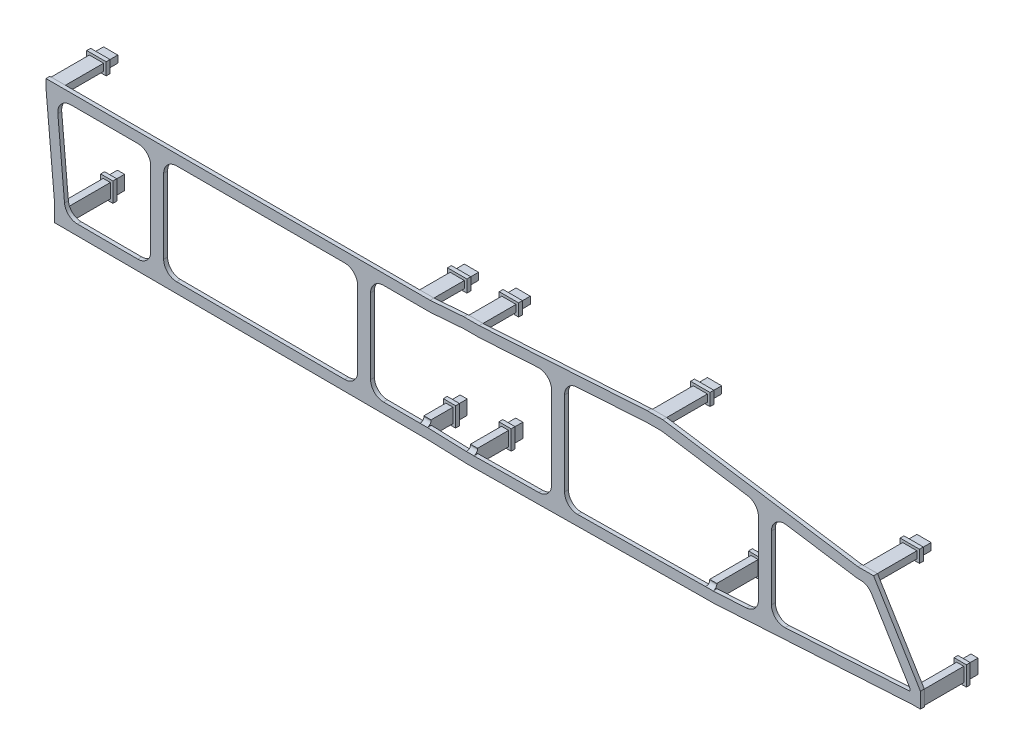
SolidWorks part; units mm, degrees
ref_plane "Front Plane" through (0, 0, 0) normal (0, 0, 1) x (1, 0, 0)
ref_plane "Top Plane" through (0, 0, 0) normal (0, 1, 0) x (1, 0, 0)
ref_plane "Right Plane" through (0, 0, 0) normal (1, 0, 0) x (0, 0, -1)
ref_plane "Plane11" through (0, 0, 7) normal (0, 0, 1) x (1, 0, 0)
ref_plane "Plane12" through (0, 0, 27) normal (0, 0, 1) x (1, 0, 0)
sketch "Sketch13" plane through (0, 0, 27) normal (0, 0, 1) x (1, 0, 0)
  line L0 (-277.75, -90) -> (-284.25, -90)
  line L1 (-284.25, -90) -> (-284.25, -78)
  line L2 (-284.25, -78) -> (-291, -3.25)
  line L3 (-291, -3.25) -> (-291, 3.25)
  line L4 (-291, 3.25) -> (-279, 3.25)
  line L5 (-279, 3.25) -> (-6, 3.25)
  line L6 (-6, 3.25) -> (6, 3.25)
  line L7 (6, 3.25) -> (32, 5.25)
  line L8 (32, 5.25) -> (44, 5.25)
  line L9 (44, 5.25) -> (174, 13.25)
  line L10 (174, 13.25) -> (186, 13.25)
  line L11 (186, 13.25) -> (337, -9.75)
  line L12 (337, -9.75) -> (349, -9.75)
  line L13 (349, -9.75) -> (385.25, -69)
  line L14 (385.25, -69) -> (385.25, -81)
  line L15 (385.25, -81) -> (378.75, -81)
  line L16 (378.75, -81) -> (225.25, -90)
  line L17 (225.25, -90) -> (218.75, -90)
  line L18 (218.75, -90) -> (40.25, -92)
  line L19 (40.25, -92) -> (33.75, -92)
  line L20 (33.75, -92) -> (4.25, -91)
  line L21 (4.25, -91) -> (-2.25, -91)
  line L22 (-2.25, -91) -> (-277.75, -90)
  line L23 (186, 13.25) -> (186, 6.75) construction
extrude "STUD LINK" add sketch "Sketch13" along normal blind 3
ref_plane "Plane1" through (0, 0, 0) normal (0, 0, 1) x (1, 0, 0)
ref_plane "Plane2" through (0, 0, -2) normal (0, 0, 1) x (1, 0, 0)
ref_plane "Plane3" through (0, 0, -8) normal (0, 0, 1) x (1, 0, 0)
ref_plane "Plane4" through (0, 0, 7) normal (0, 0, 1) x (1, 0, 0)
ref_plane "Plane5" through (0, 0, 0) normal (0, 0, 1) x (1, 0, 0)
ref_plane "Plane6" through (0, 0, -8) normal (0, 0, 1) x (1, 0, 0)
ref_plane "Plane7" through (0, 0, -7) normal (0, 0, 1) x (1, 0, 0)
ref_plane "Plane8" through (0, 0, -7) normal (0, 0, 1) x (1, 0, 0)
ref_plane "Plane9" through (0, 0, -6) normal (0, 0, 1) x (1, 0, 0)
ref_plane "Plane10" through (0, 0, -10) normal (0, 0, 1) x (1, 0, 0)
sketch "Sketch1" plane through (0, 0, 0) normal (0, 0, 1) x (1, 0, 0)
  line L8 (-5.5, 2.75) -> (-5.5, -2.75)
  line L9 (-5.5, -2.75) -> (5.5, -2.75)
  line L10 (5.5, -2.75) -> (5.5, 2.75)
  line L11 (5.5, 2.75) -> (-5.5, 2.75)
  line L12 (-5.5, 2.75) -> (-5.5, -2.75)
  line L13 (-5.5, -2.75) -> (5.5, -2.75)
  line L14 (5.5, -2.75) -> (5.5, 2.75)
  line L15 (5.5, 2.75) -> (-5.5, 2.75)
  dimension "D1" = 0.5
extrude "Boss-Extrude1" add sketch "Sketch1" against normal blind 8 and the other way up to next
sketch "Sketch2" plane through (0, 0, -2) normal (0, 0, 1) x (1, 0, 0)
  line L8 (43.5, 4.75) -> (32.5, 4.75)
  line L9 (43.5, -0.75) -> (43.5, 4.75)
  line L10 (32.5, -0.75) -> (43.5, -0.75)
  line L11 (32.5, 4.75) -> (32.5, -0.75)
  line L12 (43.5, 4.75) -> (32.5, 4.75)
  line L13 (43.5, -0.75) -> (43.5, 4.75)
  line L14 (32.5, -0.75) -> (43.5, -0.75)
  line L15 (32.5, 4.75) -> (32.5, -0.75)
  dimension "D1" = 0.5
extrude "Boss-Extrude2" add sketch "Sketch2" against normal blind 8 and the other way up to next separate body
sketch "Sketch3" plane through (0, 0, -8) normal (0, 0, 1) x (1, 0, 0)
  line L16 (185.5, 12.75) -> (174.5, 12.75)
  line L17 (185.5, 7.25) -> (185.5, 12.75)
  line L18 (174.5, 7.25) -> (185.5, 7.25)
  line L19 (174.5, 12.75) -> (174.5, 7.25)
  line L20 (185.5, 12.75) -> (174.5, 12.75)
  line L21 (185.5, 7.25) -> (185.5, 12.75)
  line L22 (174.5, 7.25) -> (185.5, 7.25)
  line L23 (174.5, 12.75) -> (174.5, 7.25)
  dimension "D1" = 0.5
extrude "Boss-Extrude3" add sketch "Sketch3" against normal blind 8 and the other way up to next separate body
sketch "Sketch4" plane through (0, 0, 7) normal (0, 0, 1) x (1, 0, 0)
  line L8 (3.75, -79.5) -> (-1.75, -79.5)
  line L9 (3.75, -90.5) -> (3.75, -79.5)
  line L10 (-1.75, -90.5) -> (3.75, -90.5)
  line L11 (-1.75, -79.5) -> (-1.75, -90.5)
  line L12 (3.75, -79.5) -> (-1.75, -79.5)
  line L13 (3.75, -90.5) -> (3.75, -79.5)
  line L14 (-1.75, -90.5) -> (3.75, -90.5)
  line L15 (-1.75, -79.5) -> (-1.75, -90.5)
  dimension "D1" = 0.5
extrude "Boss-Extrude4" add sketch "Sketch4" against normal blind 8 and the other way up to next separate body
sketch "Sketch5" plane through (0, 0, 0) normal (0, 0, 1) x (1, 0, 0)
  line L16 (34.25, -80.5) -> (34.25, -91.5)
  line L17 (39.75, -80.5) -> (34.25, -80.5)
  line L18 (39.75, -91.5) -> (39.75, -80.5)
  line L19 (34.25, -91.5) -> (39.75, -91.5)
  line L20 (34.25, -80.5) -> (34.25, -91.5)
  line L21 (39.75, -80.5) -> (34.25, -80.5)
  line L22 (39.75, -91.5) -> (39.75, -80.5)
  line L23 (34.25, -91.5) -> (39.75, -91.5)
  dimension "D1" = 0.5
extrude "Boss-Extrude5" add sketch "Sketch5" against normal blind 8 and the other way up to next separate body
sketch "Sketch6" plane through (0, 0, -8) normal (0, 0, 1) x (1, 0, 0)
  line L8 (224.75, -78.5) -> (219.25, -78.5)
  line L9 (219.25, -78.5) -> (219.25, -89.5)
  line L10 (219.25, -89.5) -> (224.75, -89.5)
  line L11 (224.75, -89.5) -> (224.75, -78.5)
  line L12 (224.75, -78.5) -> (219.25, -78.5)
  line L13 (219.25, -78.5) -> (219.25, -89.5)
  line L14 (219.25, -89.5) -> (224.75, -89.5)
  line L15 (224.75, -89.5) -> (224.75, -78.5)
  dimension "D1" = 0.5
extrude "Boss-Extrude6" add sketch "Sketch6" against normal blind 8 and the other way up to next separate body
sketch "Sketch7" plane through (0, 0, -7) normal (0, 0, 1) x (1, 0, 0)
  line L8 (348.5, -10.25) -> (337.5, -10.25)
  line L9 (348.5, -15.75) -> (348.5, -10.25)
  line L10 (337.5, -15.75) -> (348.5, -15.75)
  line L11 (337.5, -10.25) -> (337.5, -15.75)
  line L12 (348.5, -10.25) -> (337.5, -10.25)
  line L13 (348.5, -15.75) -> (348.5, -10.25)
  line L14 (337.5, -15.75) -> (348.5, -15.75)
  line L15 (337.5, -10.25) -> (337.5, -15.75)
  dimension "D1" = 0.5
extrude "Boss-Extrude7" add sketch "Sketch7" against normal blind 8 and the other way up to next separate body
sketch "Sketch8" plane through (0, 0, -7) normal (0, 0, 1) x (1, 0, 0)
  line L8 (384.75, -69.5) -> (379.25, -69.5)
  line L9 (384.75, -80.5) -> (384.75, -69.5)
  line L10 (379.25, -80.5) -> (384.75, -80.5)
  line L11 (379.25, -69.5) -> (379.25, -80.5)
  line L12 (384.75, -69.5) -> (379.25, -69.5)
  line L13 (384.75, -80.5) -> (384.75, -69.5)
  line L14 (379.25, -80.5) -> (384.75, -80.5)
  line L15 (379.25, -69.5) -> (379.25, -80.5)
  dimension "D1" = 0.5
extrude "Boss-Extrude8" add sketch "Sketch8" against normal blind 8 and the other way up to next separate body
sketch "Sketch9" plane through (0, 0, -6) normal (0, 0, 1) x (1, 0, 0)
  line L8 (-279.5, 2.75) -> (-290.5, 2.75)
  line L9 (-279.5, -2.75) -> (-279.5, 2.75)
  line L10 (-290.5, -2.75) -> (-279.5, -2.75)
  line L11 (-290.5, 2.75) -> (-290.5, -2.75)
  line L12 (-279.5, 2.75) -> (-290.5, 2.75)
  line L13 (-279.5, -2.75) -> (-279.5, 2.75)
  line L14 (-290.5, -2.75) -> (-279.5, -2.75)
  line L15 (-290.5, 2.75) -> (-290.5, -2.75)
  dimension "D1" = 0.5
extrude "Boss-Extrude9" add sketch "Sketch9" against normal blind 8 and the other way up to next separate body
sketch "Sketch10" plane through (0, 0, -10) normal (0, 0, 1) x (1, 0, 0)
  line L8 (-278.25, -78.5) -> (-283.75, -78.5)
  line L9 (-278.25, -89.5) -> (-278.25, -78.5)
  line L10 (-283.75, -89.5) -> (-278.25, -89.5)
  line L11 (-283.75, -78.5) -> (-283.75, -89.5)
  line L12 (-278.25, -78.5) -> (-283.75, -78.5)
  line L13 (-278.25, -89.5) -> (-278.25, -78.5)
  line L14 (-283.75, -89.5) -> (-278.25, -89.5)
  line L15 (-283.75, -78.5) -> (-283.75, -89.5)
  dimension "D1" = 0.5
extrude "Boss-Extrude10" add sketch "Sketch10" against normal blind 8 and the other way up to next (37 mm away) separate body
sketch "Sketch14" plane through (0, 0, 0) normal (0, 0, 1) x (1, 0, 0)
  line L8 (-7.5, -4.75) -> (7.5, -4.75)
  line L9 (7.5, -4.75) -> (7.5, 4.75)
  line L10 (7.5, 4.75) -> (-7.5, 4.75)
  line L11 (-7.5, 4.75) -> (-7.5, -4.75)
  line L12 (-7.5, -4.75) -> (7.5, -4.75)
  line L13 (7.5, -4.75) -> (7.5, 4.75)
  line L14 (7.5, 4.75) -> (-7.5, 4.75)
  line L15 (-7.5, 4.75) -> (-7.5, -4.75)
  dimension "D1" = 1.5
extrude "Boss-Extrude14" add sketch "Sketch14" along normal blind 3
sketch "Sketch15" plane through (0, 0, -2) normal (0, 0, 1) x (1, 0, 0)
  line L8 (45.5, 6.75) -> (30.5, 6.75)
  line L9 (30.5, 6.75) -> (30.5, -2.75)
  line L10 (30.5, -2.75) -> (45.5, -2.75)
  line L11 (45.5, -2.75) -> (45.5, 6.75)
  line L12 (45.5, 6.75) -> (30.5, 6.75)
  line L13 (30.5, 6.75) -> (30.5, -2.75)
  line L14 (30.5, -2.75) -> (45.5, -2.75)
  line L15 (45.5, -2.75) -> (45.5, 6.75)
  dimension "D1" = 1.5
extrude "Boss-Extrude15" add sketch "Sketch15" along normal blind 3
sketch "Sketch16" plane through (0, 0, -8) normal (0, 0, 1) x (1, 0, 0)
  line L16 (187.5, 14.75) -> (172.5, 14.75)
  line L17 (187.5, 5.25) -> (187.5, 14.75)
  line L18 (172.5, 5.25) -> (187.5, 5.25)
  line L19 (172.5, 14.75) -> (172.5, 5.25)
  line L20 (187.5, 14.75) -> (172.5, 14.75)
  line L21 (187.5, 5.25) -> (187.5, 14.75)
  line L22 (172.5, 5.25) -> (187.5, 5.25)
  line L23 (172.5, 14.75) -> (172.5, 5.25)
  dimension "D1" = 1.5
extrude "Boss-Extrude16" add sketch "Sketch16" along normal blind 3
sketch "Sketch17" plane through (0, 0, 7) normal (0, 0, 1) x (1, 0, 0)
  line L8 (5.75, -77.5) -> (-3.75, -77.5)
  line L9 (-3.75, -77.5) -> (-3.75, -92.5)
  line L10 (-3.75, -92.5) -> (5.75, -92.5)
  line L11 (5.75, -92.5) -> (5.75, -77.5)
  line L12 (5.75, -77.5) -> (-3.75, -77.5)
  line L13 (-3.75, -77.5) -> (-3.75, -92.5)
  line L14 (-3.75, -92.5) -> (5.75, -92.5)
  line L15 (5.75, -92.5) -> (5.75, -77.5)
  dimension "D1" = 1.5
extrude "Boss-Extrude17" add sketch "Sketch17" along normal blind 3
sketch "Sketch18" plane through (0, 0, 0) normal (0, 0, 1) x (1, 0, 0)
  line L8 (41.75, -78.5) -> (32.25, -78.5)
  line L9 (41.75, -93.5) -> (41.75, -78.5)
  line L10 (32.25, -93.5) -> (41.75, -93.5)
  line L11 (32.25, -78.5) -> (32.25, -93.5)
  line L16 (41.75, -78.5) -> (32.25, -78.5)
  line L17 (41.75, -93.5) -> (41.75, -78.5)
  line L18 (32.25, -93.5) -> (41.75, -93.5)
  line L19 (32.25, -78.5) -> (32.25, -93.5)
  dimension "D1" = 1.5
extrude "Boss-Extrude18" add sketch "Sketch18" along normal blind 3
sketch "Sketch19" plane through (0, 0, -8) normal (0, 0, 1) x (1, 0, 0)
  line L8 (226.75, -76.5) -> (217.25, -76.5)
  line L9 (226.75, -91.5) -> (226.75, -76.5)
  line L10 (217.25, -91.5) -> (226.75, -91.5)
  line L11 (217.25, -76.5) -> (217.25, -91.5)
  line L12 (226.75, -76.5) -> (217.25, -76.5)
  line L13 (226.75, -91.5) -> (226.75, -76.5)
  line L14 (217.25, -91.5) -> (226.75, -91.5)
  line L15 (217.25, -76.5) -> (217.25, -91.5)
  dimension "D1" = 1.5
extrude "Boss-Extrude19" add sketch "Sketch19" along normal blind 3
sketch "Sketch20" plane through (0, 0, -7) normal (0, 0, 1) x (1, 0, 0)
  line L8 (350.5, -8.25) -> (335.5, -8.25)
  line L9 (335.5, -8.25) -> (335.5, -17.75)
  line L10 (335.5, -17.75) -> (350.5, -17.75)
  line L11 (350.5, -17.75) -> (350.5, -8.25)
  line L12 (350.5, -8.25) -> (335.5, -8.25)
  line L13 (335.5, -8.25) -> (335.5, -17.75)
  line L14 (335.5, -17.75) -> (350.5, -17.75)
  line L15 (350.5, -17.75) -> (350.5, -8.25)
  dimension "D1" = 1.5
extrude "Boss-Extrude20" add sketch "Sketch20" along normal blind 3
sketch "Sketch21" plane through (0, 0, -7) normal (0, 0, 1) x (1, 0, 0)
  line L8 (386.75, -67.5) -> (377.25, -67.5)
  line L9 (386.75, -82.5) -> (386.75, -67.5)
  line L10 (377.25, -82.5) -> (386.75, -82.5)
  line L11 (377.25, -67.5) -> (377.25, -82.5)
  line L12 (386.75, -67.5) -> (377.25, -67.5)
  line L13 (386.75, -82.5) -> (386.75, -67.5)
  line L14 (377.25, -82.5) -> (386.75, -82.5)
  line L15 (377.25, -67.5) -> (377.25, -82.5)
  dimension "D1" = 1.5
extrude "Boss-Extrude21" add sketch "Sketch21" along normal blind 3
sketch "Sketch22" plane through (0, 0, -6) normal (0, 0, 1) x (1, 0, 0)
  line L8 (-277.5, 4.75) -> (-292.5, 4.75)
  line L9 (-277.5, -4.75) -> (-277.5, 4.75)
  line L10 (-292.5, -4.75) -> (-277.5, -4.75)
  line L11 (-292.5, 4.75) -> (-292.5, -4.75)
  line L12 (-277.5, 4.75) -> (-292.5, 4.75)
  line L13 (-277.5, -4.75) -> (-277.5, 4.75)
  line L14 (-292.5, -4.75) -> (-277.5, -4.75)
  line L15 (-292.5, 4.75) -> (-292.5, -4.75)
  dimension "D1" = 1.5
extrude "Boss-Extrude22" add sketch "Sketch22" along normal blind 3
sketch "Sketch23" plane through (0, 0, -10) normal (0, 0, 1) x (1, 0, 0)
  line L15 (-276.25, -76.5) -> (-285.75, -76.5)
  line L16 (-285.75, -76.5) -> (-285.75, -91.5)
  line L17 (-276.25, -91.5) -> (-276.25, -76.5)
  line L18 (-285.75, -91.5) -> (-276.25, -91.5)
  line L19 (-276.25, -76.5) -> (-285.75, -76.5)
  line L20 (-285.75, -76.5) -> (-285.75, -91.5)
  line L21 (-276.25, -91.5) -> (-276.25, -76.5)
  line L22 (-285.75, -91.5) -> (-276.25, -91.5)
  dimension "D1" = 1.5
extrude "Boss-Extrude23" add sketch "Sketch23" along normal blind 3
sketch "Sketch24" plane through (0, 0, 30) normal (0, 0, 1) x (1, 0, 0)
  line L21 (4.3856, -83) -> (33.8856, -84)
  line L22 (4.3856, -83) -> (33.8856, -84)
  line L23 (33.8856, -84) -> (40.2052, -84)
  line L24 (33.8856, -84) -> (40.2052, -84)
  line L42 (-276.25, -82.0054) -> (-2.2355, -83)
  line L43 (-2.2355, -83) -> (4.3856, -83)
  line L46 (40.2052, -84) -> (218.7052, -82)
  line L47 (218.7052, -82) -> (225.0157, -82)
  line L48 (225.0157, -82) -> (377.25, -73.0742)
  line L49 (377.25, -73.0742) -> (377.25, -71.2531)
  line L50 (377.25, -71.2531) -> (344.516, -17.75)
  line L51 (344.516, -17.75) -> (336.3942, -17.75)
  line L52 (336.3942, -17.75) -> (185.3942, 5.25)
  line L53 (185.3942, 5.25) -> (174.2459, 5.25)
  line L54 (174.2459, 5.25) -> (44.2459, -2.75)
  line L55 (44.2459, -2.75) -> (32.3072, -2.75)
  line L56 (32.3072, -2.75) -> (6.3072, -4.75)
  line L57 (6.3072, -4.75) -> (-282.832, -4.75)
  line L58 (-282.832, -4.75) -> (-276.25, -77.6395)
  line L59 (-276.25, -77.6395) -> (-276.25, -82.0054)
  line L60 (-276.25, -82.0054) -> (-2.2355, -83)
  line L61 (-2.2355, -83) -> (4.3856, -83)
  line L64 (40.2052, -84) -> (218.7052, -82)
  line L65 (218.7052, -82) -> (225.0157, -82)
  line L66 (225.0157, -82) -> (377.25, -73.0742)
  line L67 (377.25, -73.0742) -> (377.25, -71.2531)
  line L68 (377.25, -71.2531) -> (344.516, -17.75)
  line L69 (344.516, -17.75) -> (336.3942, -17.75)
  line L70 (336.3942, -17.75) -> (185.3942, 5.25)
  line L71 (185.3942, 5.25) -> (174.2459, 5.25)
  line L72 (174.2459, 5.25) -> (44.2459, -2.75)
  line L73 (44.2459, -2.75) -> (32.3072, -2.75)
  line L74 (32.3072, -2.75) -> (6.3072, -4.75)
  line L75 (6.3072, -4.75) -> (-282.832, -4.75)
  line L76 (-282.832, -4.75) -> (-276.25, -77.6395)
  line L77 (-276.25, -77.6395) -> (-276.25, -82.0054)
  dimension "D1" = 8
extrude "Cut-Extrude1" cut sketch "Sketch24" against normal blind 3
ref_plane "Plane13" through (0, -50, 0) normal (0, 1, 0) x (1, 0, 0)
sketch "Sketch25" plane through (0, -50, 0) normal (0, 1, 0) x (1, 0, 0)
  line L0 (6, -27) -> (-291, -27) construction
  line L1 (-210, -27) -> (-200, -27)
  line L2 (-210, -27) -> (-210, -30)
  line L3 (-210, -30) -> (-200, -30)
  line L4 (-200, -27) -> (-200, -30)
  line L5 (6, -30) -> (-291, -30) construction
  line L6 (174, -27) -> (44, -27) construction
  line L7 (-50, -27) -> (-40, -27)
  line L8 (-50, -27) -> (-50, -30)
  line L9 (-50, -30) -> (-40, -30)
  line L10 (-40, -27) -> (-40, -30)
  line L11 (100, -27) -> (110, -27)
  line L12 (100, -27) -> (100, -30)
  line L13 (100, -30) -> (110, -30)
  line L14 (110, -27) -> (110, -30)
  line L15 (174, -30) -> (44, -30) construction
  line L16 (337, -27) -> (186, -27) construction
  line L17 (260, -27) -> (270, -27)
  line L18 (260, -27) -> (260, -30)
  line L19 (260, -30) -> (270, -30)
  line L20 (270, -27) -> (270, -30)
  line L21 (337, -30) -> (186, -30) construction
  dimension "D1" = 10
  dimension "D2" = 150
  dimension "D3" = 40
  dimension "D4" = 100
  dimension "D5" = 150
extrude "Boss-Extrude24" add sketch "Sketch25" along normal up to next and the other way up to next
fillet "Fillet1" radius 3 3 edges at (222, -82, 27) (1, -83, 27) (37, -84, 27)
fillet "Fillet2" radius 10 20 edges at (-210, -82.2459, 28.5) (-210, -4.75, 28.5) (-282.832, -4.75, 28.5) (-276.25, -82.0054, 28.5) (100, -83.33, 28.5) (100, 0.681, 28.5) (-50, -4.75, 28.5) (-50, -82.8266, 28.5) (-40, -82.8629, 28.5) (-200, -82.2822, 28.5) (-200, -4.75, 28.5) (-40, -4.75, 28.5) (110, 1.2964, 28.5) (110, -83.218, 28.5) (270, -79.3625, 28.5) (260, -79.9488, 28.5) (260, -6.1138, 28.5) (270, -7.637, 28.5) (336.3942, -17.75, 28.5) (344.516, -17.75, 28.5)
ref_plane "Plane14" through (19, 0, 0) normal (-1, 0, 0) x (0, 0, 1)
sketch "Sketch26" plane through (19, 0, 0) normal (-1, 0, 0) x (0, 0, 1)
  line L1 (-177.7155, 99.6631) -> (210.2216, 99.6631)
  line L2 (-177.7155, 99.6631) -> (-177.7155, -244.2201)
  line L3 (-177.7155, -244.2201) -> (210.2216, -244.2201)
  line L4 (210.2216, 99.6631) -> (210.2216, -244.2201)
extrude "Cut-Extrude2" [suppressed] cut sketch "Sketch26" against normal through all
